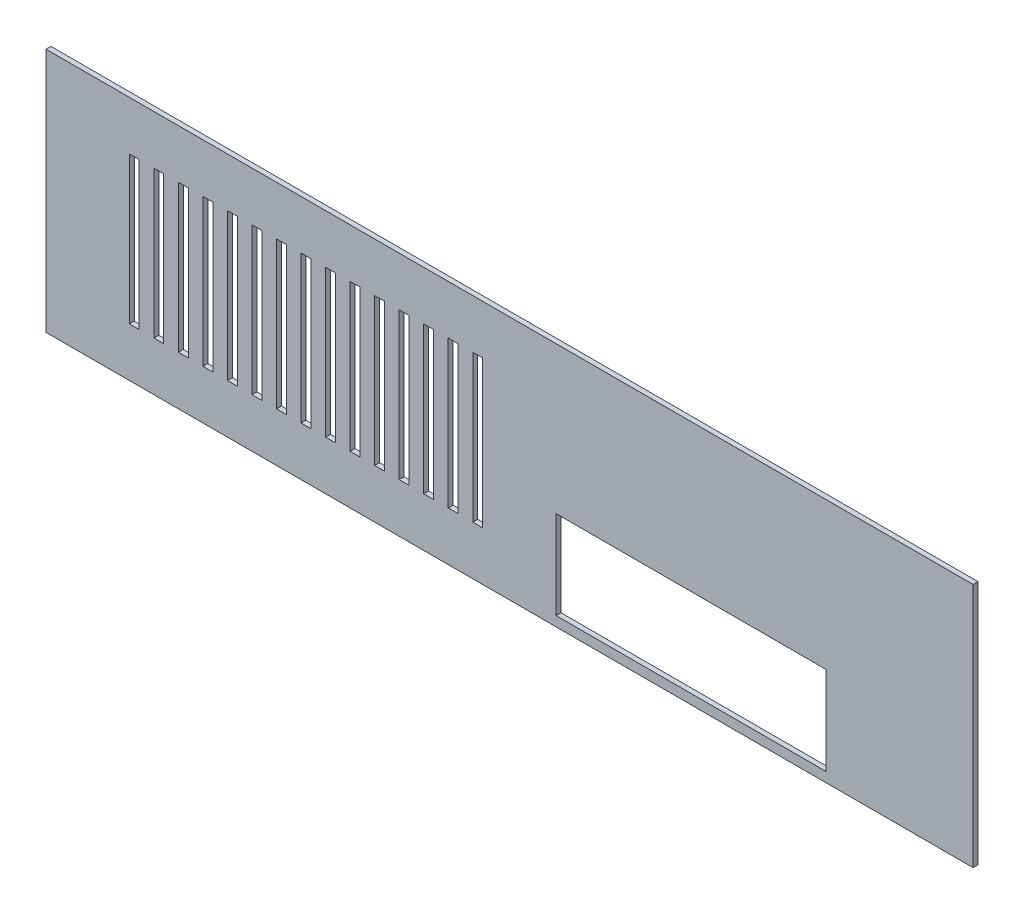
SolidWorks part; units mm, degrees
ref_plane "Front Plane" through (0, 0, 0) normal (0, 0, 1) x (1, 0, 0)
ref_plane "Top Plane" through (0, 0, 0) normal (0, 1, 0) x (1, 0, 0)
ref_plane "Right Plane" through (0, 0, 0) normal (1, 0, 0) x (0, 0, -1)
sketch "Sketch1" plane through (0, 0, 0) normal (0, 0, 1) x (1, 0, 0)
  line L1 (-61.6344, 41.198) -> (127.3656, 41.198)
  line L2 (-61.6344, 41.198) -> (-61.6344, -8.802)
  line L3 (-61.6344, -8.802) -> (127.3656, -8.802)
  line L4 (127.3656, 41.198) -> (127.3656, -8.802)
  dimension "D1" = 50
  dimension "D2" = 189
extrude "Boss-Extrude1" add sketch "Sketch1" along normal blind 1
sketch "Sketch2" plane through (0, 0, 1) normal (0, 0, 1) x (1, 0, 0)
  line L0 (-61.6344, -8.802) -> (127.3656, -8.802) construction
  line L1 (42.3656, 11.198) -> (97.3656, 11.198)
  line L2 (42.3656, 11.198) -> (42.3656, -6.802)
  line L3 (42.3656, -6.802) -> (97.3656, -6.802)
  line L4 (97.3656, 11.198) -> (97.3656, -6.802)
  line L5 (127.3656, -8.802) -> (127.3656, 41.198) construction
  dimension "D1" = 55
  dimension "D2" = 18
  dimension "D3" = 2
  dimension "D4" = 30
extrude "Cut-Extrude1" cut sketch "Sketch2" against normal through all
sketch "Sketch3" plane through (0, 0, 0) normal (0, 0, -1) x (-1, 0, 0)
  line L0 (-127.3656, 41.198) -> (61.6344, 41.198) construction
  line L1 (-27.3656, 31.198) -> (-25.3656, 31.198)
  line L2 (-27.3656, 31.198) -> (-27.3656, 1.198)
  line L3 (-27.3656, 1.198) -> (-25.3656, 1.198)
  line L4 (-25.3656, 31.198) -> (-25.3656, 1.198)
  line L5 (61.6344, -8.802) -> (-127.3656, -8.802) construction
  line L6 (-42.3656, 11.198) -> (-42.3656, -6.802) construction
  line L7 (-22.3656, 31.198) -> (-20.3656, 31.198)
  line L8 (-22.3656, 31.198) -> (-22.3656, 1.198)
  line L9 (-22.3656, 1.198) -> (-20.3656, 1.198)
  line L10 (-20.3656, 31.198) -> (-20.3656, 1.198)
  line L11 (-17.3656, 31.198) -> (-15.3656, 31.198)
  line L12 (-17.3656, 31.198) -> (-17.3656, 1.198)
  line L13 (-17.3656, 1.198) -> (-15.3656, 1.198)
  line L14 (-15.3656, 31.198) -> (-15.3656, 1.198)
  line L15 (-12.3656, 31.198) -> (-10.3656, 31.198)
  line L16 (-12.3656, 31.198) -> (-12.3656, 1.198)
  line L17 (-12.3656, 1.198) -> (-10.3656, 1.198)
  line L18 (-10.3656, 31.198) -> (-10.3656, 1.198)
  line L19 (-7.3656, 31.198) -> (-5.3656, 31.198)
  line L20 (-7.3656, 31.198) -> (-7.3656, 1.198)
  line L21 (-7.3656, 1.198) -> (-5.3656, 1.198)
  line L22 (-5.3656, 31.198) -> (-5.3656, 1.198)
  line L23 (-2.3656, 31.198) -> (-0.3656, 31.198)
  line L24 (-2.3656, 31.198) -> (-2.3656, 1.198)
  line L25 (-2.3656, 1.198) -> (-0.3656, 1.198)
  line L26 (-0.3656, 31.198) -> (-0.3656, 1.198)
  line L27 (2.6344, 31.198) -> (4.6344, 31.198)
  line L28 (2.6344, 31.198) -> (2.6344, 1.198)
  line L29 (2.6344, 1.198) -> (4.6344, 1.198)
  line L30 (4.6344, 31.198) -> (4.6344, 1.198)
  line L31 (7.6344, 31.198) -> (9.6344, 31.198)
  line L32 (7.6344, 31.198) -> (7.6344, 1.198)
  line L33 (7.6344, 1.198) -> (9.6344, 1.198)
  line L34 (9.6344, 31.198) -> (9.6344, 1.198)
  line L35 (12.6344, 31.198) -> (14.6344, 31.198)
  line L36 (12.6344, 31.198) -> (12.6344, 1.198)
  line L37 (12.6344, 1.198) -> (14.6344, 1.198)
  line L38 (14.6344, 31.198) -> (14.6344, 1.198)
  line L39 (17.6344, 31.198) -> (19.6344, 31.198)
  line L40 (17.6344, 31.198) -> (17.6344, 1.198)
  line L41 (17.6344, 1.198) -> (19.6344, 1.198)
  line L42 (19.6344, 31.198) -> (19.6344, 1.198)
  line L43 (22.6344, 31.198) -> (24.6344, 31.198)
  line L44 (22.6344, 31.198) -> (22.6344, 1.198)
  line L45 (22.6344, 1.198) -> (24.6344, 1.198)
  line L46 (24.6344, 31.198) -> (24.6344, 1.198)
  line L47 (27.6344, 31.198) -> (29.6344, 31.198)
  line L48 (27.6344, 31.198) -> (27.6344, 1.198)
  line L49 (27.6344, 1.198) -> (29.6344, 1.198)
  line L50 (29.6344, 31.198) -> (29.6344, 1.198)
  line L51 (32.6344, 31.198) -> (34.6344, 31.198)
  line L52 (32.6344, 31.198) -> (32.6344, 1.198)
  line L53 (32.6344, 1.198) -> (34.6344, 1.198)
  line L54 (34.6344, 31.198) -> (34.6344, 1.198)
  line L55 (37.6344, 31.198) -> (39.6344, 31.198)
  line L56 (37.6344, 31.198) -> (37.6344, 1.198)
  line L57 (37.6344, 1.198) -> (39.6344, 1.198)
  line L58 (39.6344, 31.198) -> (39.6344, 1.198)
  line L59 (42.6344, 31.198) -> (44.6344, 31.198)
  line L60 (42.6344, 31.198) -> (42.6344, 1.198)
  line L61 (42.6344, 1.198) -> (44.6344, 1.198)
  line L62 (44.6344, 31.198) -> (44.6344, 1.198)
  dimension "D1" = 30
  dimension "D2" = 2
  dimension "D3" = 10
  dimension "D4" = 10
  dimension "D5" = 15
  dimension "D6" = 15
extrude "Cut-Extrude2" cut sketch "Sketch3" against normal through all
